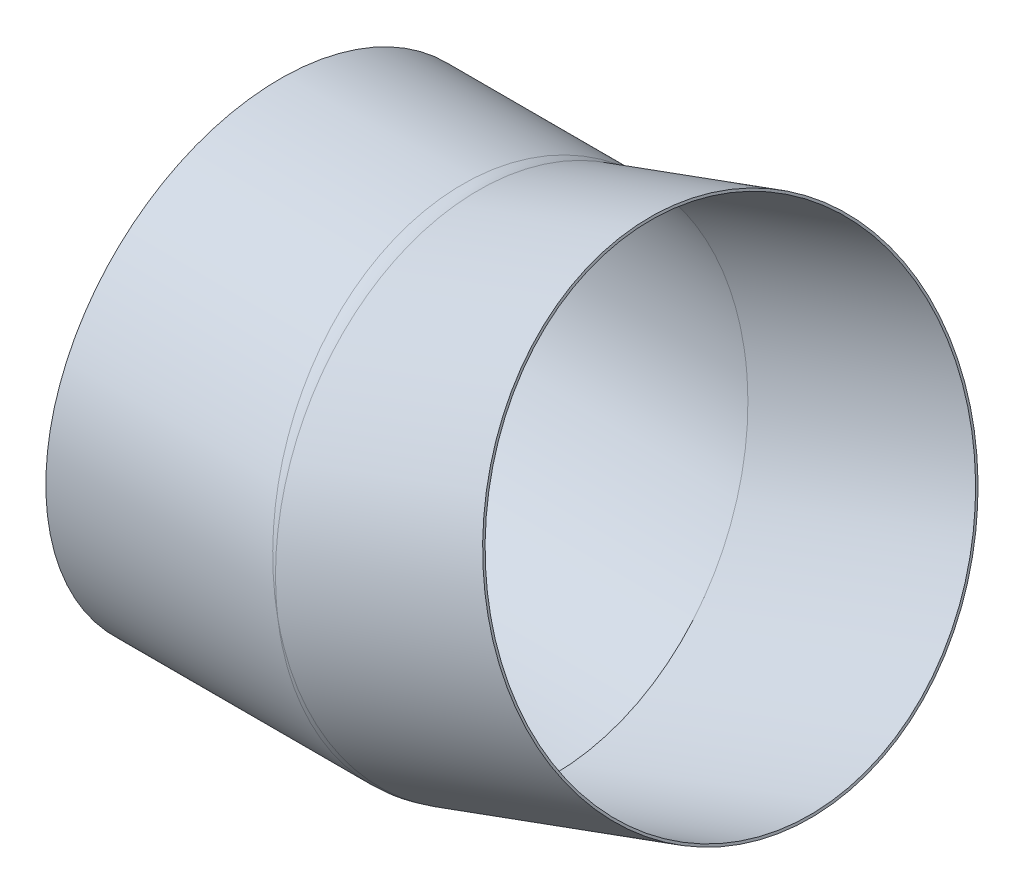
SolidWorks part; units mm, degrees
material "Gray Cast Iron"
ref_plane "Front Plane" through (0, 0, 0) normal (0, 0, 1) x (1, 0, 0)
ref_plane "Top Plane" through (0, 0, 0) normal (0, 1, 0) x (1, 0, 0)
ref_plane "Right Plane" through (0, 0, 0) normal (1, 0, 0) x (0, 0, -1)
sketch "Sketch1" plane through (0, 0, 0) normal (0, 0, 1) x (1, 0, 0)
  line L0 (0, 0) -> (100, 0)
  line L1 (100, 0) -> (193.9693, 34.202)
sketch "Sketch4" plane through (0, 0, 0) normal (1, 0, 0) x (0, 0, -1)
  circle A0 centre (0, 0) radius 100
  circle A1 centre (0, 0) radius 101
sweep "Sweep4" add profiles "Sketch4" path "Sketch1"
fillet "Fillet3" radius 20 1 edges at (117.809, -101, 0)
